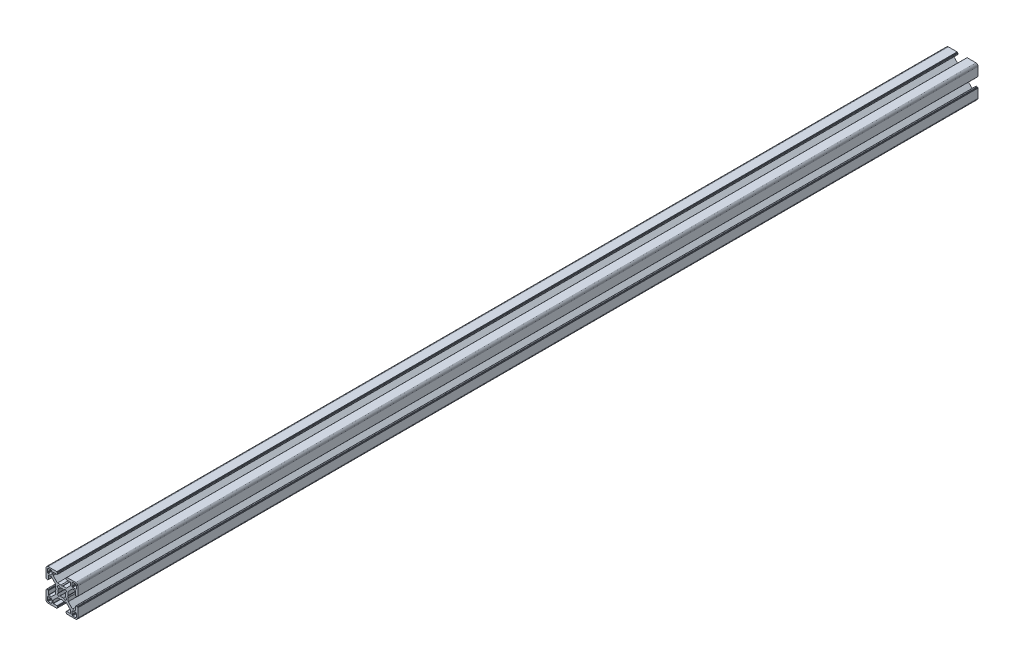
SolidWorks part; units mm, degrees
ref_plane "Front Plane" through (0, 0, 0) normal (0, 0, 1) x (1, 0, 0)
ref_plane "Top Plane" through (0, 0, 0) normal (0, 1, 0) x (1, 0, 0)
ref_plane "Right Plane" through (0, 0, 0) normal (1, 0, 0) x (0, 0, -1)
ref_plane "Plane1" through (0, 0, 0) normal (0, 0, 1) x (1, 0, 0)
sketch "Sketch1" plane through (0, 0, 0) normal (0, 0, 1) x (1, 0, 0)
  line L0 (28.3473, 29.9696) -> (28, 30)
  line L1 (28, 30) -> (19.75, 30)
  line L2 (19.75, 30) -> (19.7153, 29.997)
  line L3 (19.7153, 29.997) -> (19.6816, 29.9879)
  line L4 (19.6816, 29.9879) -> (19.65, 29.9732)
  line L5 (19.65, 29.9732) -> (19.6214, 29.9532)
  line L6 (19.6214, 29.9532) -> (19.5968, 29.9286)
  line L7 (19.5968, 29.9286) -> (19.5768, 29.9)
  line L8 (19.5768, 29.9) -> (19.5621, 29.8684)
  line L9 (19.5621, 29.8684) -> (19.553, 29.8347)
  line L10 (19.553, 29.8347) -> (19.55, 29.8)
  line L11 (19.55, 29.8) -> (19.55, 29.7)
  line L12 (19.55, 29.7) -> (19.547, 29.6653)
  line L13 (19.547, 29.6653) -> (19.5379, 29.6316)
  line L14 (19.5379, 29.6316) -> (19.5232, 29.6)
  line L15 (19.5232, 29.6) -> (19.5032, 29.5714)
  line L16 (19.5032, 29.5714) -> (19.4786, 29.5468)
  line L17 (19.4786, 29.5468) -> (19.45, 29.5268)
  line L18 (19.45, 29.5268) -> (19.4184, 29.5121)
  line L19 (19.4184, 29.5121) -> (19.3847, 29.503)
  line L20 (19.3847, 29.503) -> (19.35, 29.5)
  line L21 (19.35, 29.5) -> (19.25, 29.5)
  line L22 (19.25, 29.5) -> (19.2153, 29.497)
  line L23 (19.2153, 29.497) -> (19.1816, 29.4879)
  line L24 (19.1816, 29.4879) -> (19.15, 29.4732)
  line L25 (19.15, 29.4732) -> (19.1214, 29.4532)
  line L26 (19.1214, 29.4532) -> (19.0968, 29.4286)
  line L27 (19.0968, 29.4286) -> (19.0768, 29.4)
  line L28 (19.0768, 29.4) -> (19.0621, 29.3684)
  line L29 (19.0621, 29.3684) -> (19.053, 29.3347)
  line L30 (19.053, 29.3347) -> (19.05, 29.3)
  line L31 (19.05, 29.3) -> (19.05, 28.4)
  line L32 (19.05, 28.4) -> (19.0591, 28.2958)
  line L33 (19.0591, 28.2958) -> (19.0862, 28.1948)
  line L34 (19.0862, 28.1948) -> (19.1304, 28.1)
  line L35 (19.1304, 28.1) -> (19.1904, 28.0143)
  line L36 (19.1904, 28.0143) -> (19.2643, 27.9404)
  line L37 (19.2643, 27.9404) -> (19.35, 27.8804)
  line L38 (19.35, 27.8804) -> (19.4448, 27.8362)
  line L39 (19.4448, 27.8362) -> (19.5458, 27.8091)
  line L40 (19.5458, 27.8091) -> (19.65, 27.8)
  line L41 (19.65, 27.8) -> (23.05, 27.8)
  line L42 (23.05, 27.8) -> (23.0847, 27.7969)
  line L43 (23.0847, 27.7969) -> (23.1184, 27.7879)
  line L44 (23.1184, 27.7879) -> (23.15, 27.7732)
  line L45 (23.15, 27.7732) -> (23.1786, 27.7532)
  line L46 (23.1786, 27.7532) -> (23.2032, 27.7285)
  line L47 (23.2032, 27.7285) -> (23.2232, 27.7)
  line L48 (23.2232, 27.7) -> (23.2379, 27.6684)
  line L49 (23.2379, 27.6684) -> (23.247, 27.6347)
  line L50 (23.247, 27.6347) -> (23.25, 27.6)
  line L51 (23.25, 27.6) -> (23.25, 25.05)
  line L52 (23.25, 25.05) -> (19.2045, 21)
  line L53 (19.2045, 21) -> (15.9, 21)
  line L54 (15.9, 21) -> (15, 20.4848)
  line L55 (15, 20.4848) -> (14.1, 21)
  line L56 (14.1, 21) -> (10.7955, 21)
  line L57 (10.7955, 21) -> (7.9973, 23.8013)
  line L58 (7.9973, 23.8013) -> (6.75, 25.05)
  line L59 (6.75, 25.05) -> (6.75, 27.6)
  line L60 (6.75, 27.6) -> (6.753, 27.6347)
  line L61 (6.753, 27.6347) -> (6.7621, 27.6684)
  line L62 (6.7621, 27.6684) -> (6.7768, 27.7)
  line L63 (6.7768, 27.7) -> (6.7968, 27.7285)
  line L64 (6.7968, 27.7285) -> (6.8215, 27.7532)
  line L65 (6.8215, 27.7532) -> (6.85, 27.7732)
  line L66 (6.85, 27.7732) -> (6.8816, 27.7879)
  line L67 (6.8816, 27.7879) -> (6.9153, 27.7969)
  line L68 (6.9153, 27.7969) -> (6.95, 27.8)
  line L69 (6.95, 27.8) -> (10.35, 27.8)
  line L70 (10.35, 27.8) -> (10.4542, 27.8091)
  line L71 (10.4542, 27.8091) -> (10.5552, 27.8362)
  line L72 (10.5552, 27.8362) -> (10.65, 27.8804)
  line L73 (10.65, 27.8804) -> (10.7357, 27.9404)
  line L74 (10.7357, 27.9404) -> (10.8096, 28.0143)
  line L75 (10.8096, 28.0143) -> (10.8696, 28.1)
  line L76 (10.8696, 28.1) -> (10.9138, 28.1948)
  line L77 (10.9138, 28.1948) -> (10.9409, 28.2958)
  line L78 (10.9409, 28.2958) -> (10.95, 28.4)
  line L79 (10.95, 28.4) -> (10.95, 29.3)
  line L80 (10.95, 29.3) -> (10.947, 29.3347)
  line L81 (10.947, 29.3347) -> (10.938, 29.3684)
  line L82 (10.938, 29.3684) -> (10.9232, 29.4)
  line L83 (10.9232, 29.4) -> (10.9032, 29.4286)
  line L84 (10.9032, 29.4286) -> (10.8786, 29.4532)
  line L85 (10.8786, 29.4532) -> (10.85, 29.4732)
  line L86 (10.85, 29.4732) -> (10.8184, 29.4879)
  line L87 (10.8184, 29.4879) -> (10.7847, 29.497)
  line L88 (10.7847, 29.497) -> (10.75, 29.5)
  line L89 (10.75, 29.5) -> (10.65, 29.5)
  line L90 (10.65, 29.5) -> (10.6153, 29.503)
  line L91 (10.6153, 29.503) -> (10.5816, 29.5121)
  line L92 (10.5816, 29.5121) -> (10.55, 29.5268)
  line L93 (10.55, 29.5268) -> (10.5214, 29.5468)
  line L94 (10.5214, 29.5468) -> (10.4968, 29.5714)
  line L95 (10.4968, 29.5714) -> (10.4768, 29.6)
  line L96 (10.4768, 29.6) -> (10.4621, 29.6316)
  line L97 (10.4621, 29.6316) -> (10.453, 29.6653)
  line L98 (10.453, 29.6653) -> (10.45, 29.7)
  line L99 (10.45, 29.7) -> (10.45, 29.8)
  line L100 (10.45, 29.8) -> (10.447, 29.8347)
  line L101 (10.447, 29.8347) -> (10.4379, 29.8684)
  line L102 (10.4379, 29.8684) -> (10.4232, 29.9)
  line L103 (10.4232, 29.9) -> (10.4032, 29.9286)
  line L104 (10.4032, 29.9286) -> (10.3786, 29.9532)
  line L105 (10.3786, 29.9532) -> (10.35, 29.9732)
  line L106 (10.35, 29.9732) -> (10.3184, 29.9879)
  line L107 (10.3184, 29.9879) -> (10.2847, 29.997)
  line L108 (10.2847, 29.997) -> (10.25, 30)
  line L109 (10.25, 30) -> (2, 30)
  line L110 (2, 30) -> (1.6527, 29.9696)
  line L111 (1.6527, 29.9696) -> (1.316, 29.8794)
  line L112 (1.316, 29.8794) -> (1, 29.7321)
  line L113 (1, 29.7321) -> (0.7144, 29.5321)
  line L114 (0.7144, 29.5321) -> (0.4679, 29.2856)
  line L115 (0.4679, 29.2856) -> (0.2679, 29)
  line L116 (0.2679, 29) -> (0.1206, 28.684)
  line L117 (0.1206, 28.684) -> (0.0304, 28.3473)
  line L118 (0.0304, 28.3473) -> (0, 28)
  line L119 (0, 28) -> (0, 19.75)
  line L120 (0, 19.75) -> (0.003, 19.7153)
  line L121 (0.003, 19.7153) -> (0.0121, 19.6816)
  line L122 (0.0121, 19.6816) -> (0.0268, 19.65)
  line L123 (0.0268, 19.65) -> (0.0468, 19.6214)
  line L124 (0.0468, 19.6214) -> (0.0714, 19.5968)
  line L125 (0.0714, 19.5968) -> (0.1, 19.5768)
  line L126 (0.1, 19.5768) -> (0.1316, 19.5621)
  line L127 (0.1316, 19.5621) -> (0.1653, 19.553)
  line L128 (0.1653, 19.553) -> (0.2, 19.55)
  line L129 (0.2, 19.55) -> (0.3, 19.55)
  line L130 (0.3, 19.55) -> (0.3347, 19.547)
  line L131 (0.3347, 19.547) -> (0.3684, 19.5379)
  line L132 (0.3684, 19.5379) -> (0.4, 19.5232)
  line L133 (0.4, 19.5232) -> (0.4286, 19.5032)
  line L134 (0.4286, 19.5032) -> (0.4532, 19.4786)
  line L135 (0.4532, 19.4786) -> (0.4732, 19.45)
  line L136 (0.4732, 19.45) -> (0.4879, 19.4184)
  line L137 (0.4879, 19.4184) -> (0.497, 19.3847)
  line L138 (0.497, 19.3847) -> (0.5, 19.35)
  line L139 (0.5, 19.35) -> (0.5, 19.25)
  line L140 (0.5, 19.25) -> (0.503, 19.2153)
  line L141 (0.503, 19.2153) -> (0.5121, 19.1816)
  line L142 (0.5121, 19.1816) -> (0.5268, 19.15)
  line L143 (0.5268, 19.15) -> (0.5468, 19.1214)
  line L144 (0.5468, 19.1214) -> (0.5714, 19.0968)
  line L145 (0.5714, 19.0968) -> (0.6, 19.0768)
  line L146 (0.6, 19.0768) -> (0.6316, 19.0621)
  line L147 (0.6316, 19.0621) -> (0.6653, 19.053)
  line L148 (0.6653, 19.053) -> (0.7, 19.05)
  line L149 (0.7, 19.05) -> (1.6, 19.05)
  line L150 (1.6, 19.05) -> (1.7042, 19.0591)
  line L151 (1.7042, 19.0591) -> (1.8052, 19.0862)
  line L152 (1.8052, 19.0862) -> (1.9, 19.1304)
  line L153 (1.9, 19.1304) -> (1.9857, 19.1904)
  line L154 (1.9857, 19.1904) -> (2.0596, 19.2643)
  line L155 (2.0596, 19.2643) -> (2.1196, 19.35)
  line L156 (2.1196, 19.35) -> (2.1638, 19.4448)
  line L157 (2.1638, 19.4448) -> (2.1909, 19.5458)
  line L158 (2.1909, 19.5458) -> (2.2, 19.65)
  line L159 (2.2, 19.65) -> (2.2, 23.05)
  line L160 (2.2, 23.05) -> (2.203, 23.0847)
  line L161 (2.203, 23.0847) -> (2.2121, 23.1184)
  line L162 (2.2121, 23.1184) -> (2.2268, 23.15)
  line L163 (2.2268, 23.15) -> (2.2468, 23.1786)
  line L164 (2.2468, 23.1786) -> (2.2714, 23.2032)
  line L165 (2.2714, 23.2032) -> (2.3, 23.2232)
  line L166 (2.3, 23.2232) -> (2.3316, 23.2379)
  line L167 (2.3316, 23.2379) -> (2.3653, 23.247)
  line L168 (2.3653, 23.247) -> (2.4, 23.25)
  line L169 (2.4, 23.25) -> (4.95, 23.25)
  line L170 (4.95, 23.25) -> (7.9973, 20.2027)
  line L171 (7.9973, 20.2027) -> (8.9955, 19.2045)
  line L172 (8.9955, 19.2045) -> (8.9955, 15.9)
  line L173 (8.9955, 15.9) -> (9.5151, 15)
  line L174 (9.5151, 15) -> (8.9955, 14.1)
  line L175 (8.9955, 14.1) -> (8.9955, 10.7955)
  line L176 (8.9955, 10.7955) -> (4.95, 6.75)
  line L177 (4.95, 6.75) -> (2.4, 6.75)
  line L178 (2.4, 6.75) -> (2.3653, 6.753)
  line L179 (2.3653, 6.753) -> (2.3316, 6.7621)
  line L180 (2.3316, 6.7621) -> (2.3, 6.7768)
  line L181 (2.3, 6.7768) -> (2.2714, 6.7968)
  line L182 (2.2714, 6.7968) -> (2.2468, 6.8214)
  line L183 (2.2468, 6.8214) -> (2.2268, 6.85)
  line L184 (2.2268, 6.85) -> (2.2121, 6.8816)
  line L185 (2.2121, 6.8816) -> (2.203, 6.9153)
  line L186 (2.203, 6.9153) -> (2.2, 6.95)
  line L187 (2.2, 6.95) -> (2.2, 10.35)
  line L188 (2.2, 10.35) -> (2.1909, 10.4542)
  line L189 (2.1909, 10.4542) -> (2.1638, 10.5552)
  line L190 (2.1638, 10.5552) -> (2.1196, 10.65)
  line L191 (2.1196, 10.65) -> (2.0596, 10.7357)
  line L192 (2.0596, 10.7357) -> (1.9857, 10.8096)
  line L193 (1.9857, 10.8096) -> (1.9, 10.8696)
  line L194 (1.9, 10.8696) -> (1.8052, 10.9138)
  line L195 (1.8052, 10.9138) -> (1.7042, 10.9409)
  line L196 (1.7042, 10.9409) -> (1.6, 10.95)
  line L197 (1.6, 10.95) -> (0.7, 10.95)
  line L198 (0.7, 10.95) -> (0.6653, 10.9469)
  line L199 (0.6653, 10.9469) -> (0.6316, 10.9379)
  line L200 (0.6316, 10.9379) -> (0.6, 10.9232)
  line L201 (0.6, 10.9232) -> (0.5715, 10.9032)
  line L202 (0.5715, 10.9032) -> (0.5468, 10.8785)
  line L203 (0.5468, 10.8785) -> (0.5268, 10.85)
  line L204 (0.5268, 10.85) -> (0.5121, 10.8184)
  line L205 (0.5121, 10.8184) -> (0.503, 10.7847)
  line L206 (0.503, 10.7847) -> (0.5, 10.75)
  line L207 (0.5, 10.75) -> (0.5, 10.65)
  line L208 (0.5, 10.65) -> (0.497, 10.6153)
  line L209 (0.497, 10.6153) -> (0.4879, 10.5816)
  line L210 (0.4879, 10.5816) -> (0.4732, 10.55)
  line L211 (0.4732, 10.55) -> (0.4532, 10.5214)
  line L212 (0.4532, 10.5214) -> (0.4286, 10.4968)
  line L213 (0.4286, 10.4968) -> (0.4, 10.4768)
  line L214 (0.4, 10.4768) -> (0.3684, 10.4621)
  line L215 (0.3684, 10.4621) -> (0.3347, 10.453)
  line L216 (0.3347, 10.453) -> (0.3, 10.45)
  line L217 (0.3, 10.45) -> (0.2, 10.45)
  line L218 (0.2, 10.45) -> (0.1653, 10.447)
  line L219 (0.1653, 10.447) -> (0.1316, 10.4379)
  line L220 (0.1316, 10.4379) -> (0.1, 10.4232)
  line L221 (0.1, 10.4232) -> (0.0714, 10.4032)
  line L222 (0.0714, 10.4032) -> (0.0468, 10.3786)
  line L223 (0.0468, 10.3786) -> (0.0268, 10.35)
  line L224 (0.0268, 10.35) -> (0.0121, 10.3184)
  line L225 (0.0121, 10.3184) -> (0.003, 10.2847)
  line L226 (0.003, 10.2847) -> (0, 10.25)
  line L227 (0, 10.25) -> (0, 2)
  line L228 (0, 2) -> (0.0304, 1.6527)
  line L229 (0.0304, 1.6527) -> (0.1206, 1.316)
  line L230 (0.1206, 1.316) -> (0.2679, 1)
  line L231 (0.2679, 1) -> (0.4679, 0.7144)
  line L232 (0.4679, 0.7144) -> (0.7144, 0.4679)
  line L233 (0.7144, 0.4679) -> (1, 0.2679)
  line L234 (1, 0.2679) -> (1.316, 0.1206)
  line L235 (1.316, 0.1206) -> (1.6527, 0.0304)
  line L236 (1.6527, 0.0304) -> (2, 0)
  line L237 (2, 0) -> (10.25, 0)
  line L238 (10.25, 0) -> (10.2847, 0.003)
  line L239 (10.2847, 0.003) -> (10.3184, 0.0121)
  line L240 (10.3184, 0.0121) -> (10.35, 0.0268)
  line L241 (10.35, 0.0268) -> (10.3786, 0.0468)
  line L242 (10.3786, 0.0468) -> (10.4032, 0.0714)
  line L243 (10.4032, 0.0714) -> (10.4232, 0.1)
  line L244 (10.4232, 0.1) -> (10.4379, 0.1316)
  line L245 (10.4379, 0.1316) -> (10.447, 0.1653)
  line L246 (10.447, 0.1653) -> (10.45, 0.2)
  line L247 (10.45, 0.2) -> (10.45, 0.3)
  line L248 (10.45, 0.3) -> (10.453, 0.3347)
  line L249 (10.453, 0.3347) -> (10.4621, 0.3684)
  line L250 (10.4621, 0.3684) -> (10.4768, 0.4)
  line L251 (10.4768, 0.4) -> (10.4968, 0.4286)
  line L252 (10.4968, 0.4286) -> (10.5214, 0.4532)
  line L253 (10.5214, 0.4532) -> (10.55, 0.4732)
  line L254 (10.55, 0.4732) -> (10.5816, 0.4879)
  line L255 (10.5816, 0.4879) -> (10.6153, 0.497)
  line L256 (10.6153, 0.497) -> (10.65, 0.5)
  line L257 (10.65, 0.5) -> (10.75, 0.5)
  line L258 (10.75, 0.5) -> (10.7847, 0.503)
  line L259 (10.7847, 0.503) -> (10.8184, 0.5121)
  line L260 (10.8184, 0.5121) -> (10.85, 0.5268)
  line L261 (10.85, 0.5268) -> (10.8785, 0.5468)
  line L262 (10.8785, 0.5468) -> (10.9032, 0.5715)
  line L263 (10.9032, 0.5715) -> (10.9232, 0.6)
  line L264 (10.9232, 0.6) -> (10.9379, 0.6316)
  line L265 (10.9379, 0.6316) -> (10.9469, 0.6653)
  line L266 (10.9469, 0.6653) -> (10.95, 0.7)
  line L267 (10.95, 0.7) -> (10.95, 1.6)
  line L268 (10.95, 1.6) -> (10.9409, 1.7042)
  line L269 (10.9409, 1.7042) -> (10.9138, 1.8052)
  line L270 (10.9138, 1.8052) -> (10.8696, 1.9)
  line L271 (10.8696, 1.9) -> (10.8096, 1.9857)
  line L272 (10.8096, 1.9857) -> (10.7357, 2.0596)
  line L273 (10.7357, 2.0596) -> (10.65, 2.1196)
  line L274 (10.65, 2.1196) -> (10.5552, 2.1638)
  line L275 (10.5552, 2.1638) -> (10.4542, 2.1909)
  line L276 (10.4542, 2.1909) -> (10.35, 2.2)
  line L277 (10.35, 2.2) -> (6.95, 2.2)
  line L278 (6.95, 2.2) -> (6.9153, 2.203)
  line L279 (6.9153, 2.203) -> (6.8816, 2.212)
  line L280 (6.8816, 2.212) -> (6.85, 2.2268)
  line L281 (6.85, 2.2268) -> (6.8215, 2.2468)
  line L282 (6.8215, 2.2468) -> (6.7968, 2.2714)
  line L283 (6.7968, 2.2714) -> (6.7768, 2.3)
  line L284 (6.7768, 2.3) -> (6.7621, 2.3316)
  line L285 (6.7621, 2.3316) -> (6.753, 2.3653)
  line L286 (6.753, 2.3653) -> (6.75, 2.4)
  line L287 (6.75, 2.4) -> (6.75, 4.95)
  line L288 (6.75, 4.95) -> (9.7875, 7.9908)
  line L289 (9.7875, 7.9908) -> (10.7955, 9)
  line L290 (10.7955, 9) -> (14.1, 9)
  line L291 (14.1, 9) -> (15, 9.5151)
  line L292 (15, 9.5151) -> (15.9, 9)
  line L293 (15.9, 9) -> (19.2045, 9)
  line L294 (19.2045, 9) -> (20.2126, 7.9908)
  line L295 (20.2126, 7.9908) -> (23.25, 4.95)
  line L296 (23.25, 4.95) -> (23.25, 2.4)
  line L297 (23.25, 2.4) -> (23.247, 2.3653)
  line L298 (23.247, 2.3653) -> (23.2379, 2.3316)
  line L299 (23.2379, 2.3316) -> (23.2232, 2.3)
  line L300 (23.2232, 2.3) -> (23.2032, 2.2714)
  line L301 (23.2032, 2.2714) -> (23.1786, 2.2468)
  line L302 (23.1786, 2.2468) -> (23.15, 2.2268)
  line L303 (23.15, 2.2268) -> (23.1184, 2.212)
  line L304 (23.1184, 2.212) -> (23.0847, 2.203)
  line L305 (23.0847, 2.203) -> (23.05, 2.2)
  line L306 (23.05, 2.2) -> (19.65, 2.2)
  line L307 (19.65, 2.2) -> (19.5458, 2.1909)
  line L308 (19.5458, 2.1909) -> (19.4448, 2.1638)
  line L309 (19.4448, 2.1638) -> (19.35, 2.1196)
  line L310 (19.35, 2.1196) -> (19.2643, 2.0596)
  line L311 (19.2643, 2.0596) -> (19.1904, 1.9857)
  line L312 (19.1904, 1.9857) -> (19.1304, 1.9)
  line L313 (19.1304, 1.9) -> (19.0862, 1.8052)
  line L314 (19.0862, 1.8052) -> (19.0591, 1.7042)
  line L315 (19.0591, 1.7042) -> (19.05, 1.6)
  line L316 (19.05, 1.6) -> (19.05, 0.7)
  line L317 (19.05, 0.7) -> (19.053, 0.6653)
  line L318 (19.053, 0.6653) -> (19.0621, 0.6316)
  line L319 (19.0621, 0.6316) -> (19.0768, 0.6)
  line L320 (19.0768, 0.6) -> (19.0968, 0.5714)
  line L321 (19.0968, 0.5714) -> (19.1214, 0.5468)
  line L322 (19.1214, 0.5468) -> (19.15, 0.5268)
  line L323 (19.15, 0.5268) -> (19.1816, 0.5121)
  line L324 (19.1816, 0.5121) -> (19.2153, 0.503)
  line L325 (19.2153, 0.503) -> (19.25, 0.5)
  line L326 (19.25, 0.5) -> (19.35, 0.5)
  line L327 (19.35, 0.5) -> (19.3847, 0.497)
  line L328 (19.3847, 0.497) -> (19.4184, 0.4879)
  line L329 (19.4184, 0.4879) -> (19.45, 0.4732)
  line L330 (19.45, 0.4732) -> (19.4786, 0.4532)
  line L331 (19.4786, 0.4532) -> (19.5032, 0.4286)
  line L332 (19.5032, 0.4286) -> (19.5232, 0.4)
  line L333 (19.5232, 0.4) -> (19.5379, 0.3684)
  line L334 (19.5379, 0.3684) -> (19.547, 0.3347)
  line L335 (19.547, 0.3347) -> (19.55, 0.3)
  line L336 (19.55, 0.3) -> (19.55, 0.2)
  line L337 (19.55, 0.2) -> (19.553, 0.1653)
  line L338 (19.553, 0.1653) -> (19.5621, 0.1316)
  line L339 (19.5621, 0.1316) -> (19.5768, 0.1)
  line L340 (19.5768, 0.1) -> (19.5968, 0.0714)
  line L341 (19.5968, 0.0714) -> (19.6214, 0.0468)
  line L342 (19.6214, 0.0468) -> (19.65, 0.0268)
  line L343 (19.65, 0.0268) -> (19.6816, 0.0121)
  line L344 (19.6816, 0.0121) -> (19.7153, 0.003)
  line L345 (19.7153, 0.003) -> (19.75, 0)
  line L346 (19.75, 0) -> (28, 0)
  line L347 (28, 0) -> (28.3473, 0.0304)
  line L348 (28.3473, 0.0304) -> (28.684, 0.1206)
  line L349 (28.684, 0.1206) -> (29, 0.2679)
  line L350 (29, 0.2679) -> (29.2856, 0.4679)
  line L351 (29.2856, 0.4679) -> (29.5321, 0.7144)
  line L352 (29.5321, 0.7144) -> (29.7321, 1)
  line L353 (29.7321, 1) -> (29.8794, 1.316)
  line L354 (29.8794, 1.316) -> (29.9696, 1.6527)
  line L355 (29.9696, 1.6527) -> (30, 2)
  line L356 (30, 2) -> (30, 10.25)
  line L357 (30, 10.25) -> (29.997, 10.2847)
  line L358 (29.997, 10.2847) -> (29.988, 10.3184)
  line L359 (29.988, 10.3184) -> (29.9732, 10.35)
  line L360 (29.9732, 10.35) -> (29.9532, 10.3785)
  line L361 (29.9532, 10.3785) -> (29.9286, 10.4032)
  line L362 (29.9286, 10.4032) -> (29.9, 10.4232)
  line L363 (29.9, 10.4232) -> (29.8684, 10.4379)
  line L364 (29.8684, 10.4379) -> (29.8347, 10.447)
  line L365 (29.8347, 10.447) -> (29.8, 10.45)
  line L366 (29.8, 10.45) -> (29.7, 10.45)
  line L367 (29.7, 10.45) -> (29.6649, 10.4534)
  line L368 (29.6649, 10.4534) -> (29.6312, 10.4624)
  line L369 (29.6312, 10.4624) -> (29.5996, 10.4772)
  line L370 (29.5996, 10.4772) -> (29.5711, 10.4972)
  line L371 (29.5711, 10.4972) -> (29.5464, 10.5218)
  line L372 (29.5464, 10.5218) -> (29.5264, 10.5504)
  line L373 (29.5264, 10.5504) -> (29.5117, 10.582)
  line L374 (29.5117, 10.582) -> (29.5027, 10.6156)
  line L375 (29.5027, 10.6156) -> (29.4996, 10.6504)
  line L376 (29.4996, 10.6504) -> (29.4996, 10.7504)
  line L377 (29.4996, 10.7504) -> (29.497, 10.7847)
  line L378 (29.497, 10.7847) -> (29.4879, 10.8184)
  line L379 (29.4879, 10.8184) -> (29.4732, 10.85)
  line L380 (29.4732, 10.85) -> (29.4532, 10.8785)
  line L381 (29.4532, 10.8785) -> (29.4286, 10.9032)
  line L382 (29.4286, 10.9032) -> (29.4, 10.9232)
  line L383 (29.4, 10.9232) -> (29.3684, 10.9379)
  line L384 (29.3684, 10.9379) -> (29.3347, 10.9469)
  line L385 (29.3347, 10.9469) -> (29.3, 10.95)
  line L386 (29.3, 10.95) -> (28.4, 10.95)
  line L387 (28.4, 10.95) -> (28.2958, 10.9409)
  line L388 (28.2958, 10.9409) -> (28.1948, 10.9138)
  line L389 (28.1948, 10.9138) -> (28.1, 10.8696)
  line L390 (28.1, 10.8696) -> (28.0143, 10.8096)
  line L391 (28.0143, 10.8096) -> (27.9404, 10.7357)
  line L392 (27.9404, 10.7357) -> (27.8804, 10.65)
  line L393 (27.8804, 10.65) -> (27.8362, 10.5552)
  line L394 (27.8362, 10.5552) -> (27.8091, 10.4542)
  line L395 (27.8091, 10.4542) -> (27.8, 10.35)
  line L396 (27.8, 10.35) -> (27.8, 6.95)
  line L397 (27.8, 6.95) -> (27.797, 6.9153)
  line L398 (27.797, 6.9153) -> (27.7879, 6.8816)
  line L399 (27.7879, 6.8816) -> (27.7732, 6.85)
  line L400 (27.7732, 6.85) -> (27.7532, 6.8214)
  line L401 (27.7532, 6.8214) -> (27.7286, 6.7968)
  line L402 (27.7286, 6.7968) -> (27.7, 6.7768)
  line L403 (27.7, 6.7768) -> (27.6684, 6.7621)
  line L404 (27.6684, 6.7621) -> (27.6347, 6.753)
  line L405 (27.6347, 6.753) -> (27.6, 6.75)
  line L406 (27.6, 6.75) -> (25.05, 6.75)
  line L407 (25.05, 6.75) -> (23.8092, 7.9908)
  line L408 (23.8092, 7.9908) -> (21.0045, 10.7955)
  line L409 (21.0045, 10.7955) -> (21.0045, 14.1)
  line L410 (21.0045, 14.1) -> (20.4849, 15)
  line L411 (20.4849, 15) -> (21.0045, 15.9)
  line L412 (21.0045, 15.9) -> (21.0045, 19.2045)
  line L413 (21.0045, 19.2045) -> (25.05, 23.25)
  line L414 (25.05, 23.25) -> (27.6, 23.25)
  line L415 (27.6, 23.25) -> (27.6347, 23.247)
  line L416 (27.6347, 23.247) -> (27.6684, 23.2379)
  line L417 (27.6684, 23.2379) -> (27.7, 23.2232)
  line L418 (27.7, 23.2232) -> (27.7286, 23.2032)
  line L419 (27.7286, 23.2032) -> (27.7532, 23.1786)
  line L420 (27.7532, 23.1786) -> (27.7732, 23.15)
  line L421 (27.7732, 23.15) -> (27.7879, 23.1184)
  line L422 (27.7879, 23.1184) -> (27.797, 23.0847)
  line L423 (27.797, 23.0847) -> (27.8, 23.05)
  line L424 (27.8, 23.05) -> (27.8, 19.65)
  line L425 (27.8, 19.65) -> (27.8091, 19.5458)
  line L426 (27.8091, 19.5458) -> (27.8362, 19.4448)
  line L427 (27.8362, 19.4448) -> (27.8804, 19.35)
  line L428 (27.8804, 19.35) -> (27.9404, 19.2643)
  line L429 (27.9404, 19.2643) -> (28.0143, 19.1904)
  line L430 (28.0143, 19.1904) -> (28.1, 19.1304)
  line L431 (28.1, 19.1304) -> (28.1948, 19.0862)
  line L432 (28.1948, 19.0862) -> (28.2958, 19.0591)
  line L433 (28.2958, 19.0591) -> (28.4, 19.05)
  line L434 (28.4, 19.05) -> (29.3, 19.05)
  line L435 (29.3, 19.05) -> (29.3347, 19.053)
  line L436 (29.3347, 19.053) -> (29.3684, 19.0621)
  line L437 (29.3684, 19.0621) -> (29.4, 19.0768)
  line L438 (29.4, 19.0768) -> (29.4282, 19.0971)
  line L439 (29.4282, 19.0971) -> (29.4528, 19.1218)
  line L440 (29.4528, 19.1218) -> (29.4728, 19.1504)
  line L441 (29.4728, 19.1504) -> (29.4876, 19.182)
  line L442 (29.4876, 19.182) -> (29.4966, 19.2156)
  line L443 (29.4966, 19.2156) -> (29.4996, 19.2504)
  line L444 (29.4996, 19.2504) -> (29.4996, 19.3504)
  line L445 (29.4996, 19.3504) -> (29.5027, 19.3851)
  line L446 (29.5027, 19.3851) -> (29.5117, 19.4188)
  line L447 (29.5117, 19.4188) -> (29.5264, 19.4504)
  line L448 (29.5264, 19.4504) -> (29.5464, 19.4789)
  line L449 (29.5464, 19.4789) -> (29.5711, 19.5036)
  line L450 (29.5711, 19.5036) -> (29.5996, 19.5236)
  line L451 (29.5996, 19.5236) -> (29.6312, 19.5383)
  line L452 (29.6312, 19.5383) -> (29.6649, 19.5473)
  line L453 (29.6649, 19.5473) -> (29.7, 19.55)
  line L454 (29.7, 19.55) -> (29.8, 19.55)
  line L455 (29.8, 19.55) -> (29.8347, 19.553)
  line L456 (29.8347, 19.553) -> (29.8684, 19.5621)
  line L457 (29.8684, 19.5621) -> (29.9, 19.5768)
  line L458 (29.9, 19.5768) -> (29.9286, 19.5968)
  line L459 (29.9286, 19.5968) -> (29.9532, 19.6214)
  line L460 (29.9532, 19.6214) -> (29.9732, 19.65)
  line L461 (29.9732, 19.65) -> (29.9879, 19.6816)
  line L462 (29.9879, 19.6816) -> (29.997, 19.7153)
  line L463 (29.997, 19.7153) -> (30, 19.75)
  line L464 (30, 19.75) -> (30, 28)
  line L465 (30, 28) -> (29.9696, 28.3473)
  line L466 (29.9696, 28.3473) -> (29.8794, 28.684)
  line L467 (29.8794, 28.684) -> (29.7321, 29)
  line L468 (29.7321, 29) -> (29.5321, 29.2856)
  line L469 (29.5321, 29.2856) -> (29.2856, 29.5321)
  line L470 (29.2856, 29.5321) -> (29, 29.7321)
  line L471 (29, 29.7321) -> (28.684, 29.8794)
  line L472 (28.684, 29.8794) -> (28.3473, 29.9696)
  line L473 (1.3, 25.5) -> (1.3, 27.7)
  line L474 (1.3, 27.7) -> (1.3123, 27.8564)
  line L475 (1.3123, 27.8564) -> (1.3489, 28.009)
  line L476 (1.3489, 28.009) -> (1.409, 28.154)
  line L477 (1.409, 28.154) -> (1.491, 28.2878)
  line L478 (1.491, 28.2878) -> (1.5929, 28.4071)
  line L479 (1.5929, 28.4071) -> (1.7122, 28.509)
  line L480 (1.7122, 28.509) -> (1.846, 28.591)
  line L481 (1.846, 28.591) -> (1.991, 28.6511)
  line L482 (1.991, 28.6511) -> (2.1436, 28.6877)
  line L483 (2.1436, 28.6877) -> (2.3, 28.7)
  line L484 (2.3, 28.7) -> (4.5, 28.7)
  line L485 (4.5, 28.7) -> (4.6564, 28.6877)
  line L486 (4.6564, 28.6877) -> (4.809, 28.6511)
  line L487 (4.809, 28.6511) -> (4.954, 28.591)
  line L488 (4.954, 28.591) -> (5.0878, 28.509)
  line L489 (5.0878, 28.509) -> (5.2071, 28.4071)
  line L490 (5.2071, 28.4071) -> (5.309, 28.2878)
  line L491 (5.309, 28.2878) -> (5.391, 28.154)
  line L492 (5.391, 28.154) -> (5.4511, 28.009)
  line L493 (5.4511, 28.009) -> (5.4877, 27.8564)
  line L494 (5.4877, 27.8564) -> (5.5, 27.7)
  line L495 (5.5, 27.7) -> (5.5, 25.5)
  line L496 (5.5, 25.5) -> (5.4877, 25.3436)
  line L497 (5.4877, 25.3436) -> (5.4511, 25.191)
  line L498 (5.4511, 25.191) -> (5.391, 25.046)
  line L499 (5.391, 25.046) -> (5.309, 24.9122)
  line L500 (5.309, 24.9122) -> (5.2071, 24.7929)
  line L501 (5.2071, 24.7929) -> (5.0878, 24.691)
  line L502 (5.0878, 24.691) -> (4.954, 24.609)
  line L503 (4.954, 24.609) -> (4.809, 24.5489)
  line L504 (4.809, 24.5489) -> (4.6564, 24.5123)
  line L505 (4.6564, 24.5123) -> (4.5, 24.5)
  line L506 (4.5, 24.5) -> (2.3, 24.5)
  line L507 (2.3, 24.5) -> (2.1436, 24.5123)
  line L508 (2.1436, 24.5123) -> (1.991, 24.5489)
  line L509 (1.991, 24.5489) -> (1.846, 24.609)
  line L510 (1.846, 24.609) -> (1.7122, 24.691)
  line L511 (1.7122, 24.691) -> (1.5929, 24.7929)
  line L512 (1.5929, 24.7929) -> (1.491, 24.9122)
  line L513 (1.491, 24.9122) -> (1.409, 25.046)
  line L514 (1.409, 25.046) -> (1.3489, 25.191)
  line L515 (1.3489, 25.191) -> (1.3123, 25.3436)
  line L516 (1.3123, 25.3436) -> (1.3, 25.5)
  line L517 (25.3436, 28.6877) -> (25.5, 28.7)
  line L518 (25.5, 28.7) -> (27.7, 28.7)
  line L519 (27.7, 28.7) -> (27.8564, 28.6877)
  line L520 (27.8564, 28.6877) -> (28.009, 28.6511)
  line L521 (28.009, 28.6511) -> (28.154, 28.591)
  line L522 (28.154, 28.591) -> (28.2878, 28.509)
  line L523 (28.2878, 28.509) -> (28.4071, 28.4071)
  line L524 (28.4071, 28.4071) -> (28.509, 28.2878)
  line L525 (28.509, 28.2878) -> (28.591, 28.154)
  line L526 (28.591, 28.154) -> (28.6511, 28.009)
  line L527 (28.6511, 28.009) -> (28.6877, 27.8564)
  line L528 (28.6877, 27.8564) -> (28.7, 27.7)
  line L529 (28.7, 27.7) -> (28.7, 25.5)
  line L530 (28.7, 25.5) -> (28.6877, 25.3436)
  line L531 (28.6877, 25.3436) -> (28.6511, 25.191)
  line L532 (28.6511, 25.191) -> (28.591, 25.046)
  line L533 (28.591, 25.046) -> (28.509, 24.9122)
  line L534 (28.509, 24.9122) -> (28.4071, 24.7929)
  line L535 (28.4071, 24.7929) -> (28.2878, 24.691)
  line L536 (28.2878, 24.691) -> (28.154, 24.609)
  line L537 (28.154, 24.609) -> (28.009, 24.5489)
  line L538 (28.009, 24.5489) -> (27.8564, 24.5123)
  line L539 (27.8564, 24.5123) -> (27.7, 24.5)
  line L540 (27.7, 24.5) -> (25.5, 24.5)
  line L541 (25.5, 24.5) -> (25.3436, 24.5123)
  line L542 (25.3436, 24.5123) -> (25.191, 24.5489)
  line L543 (25.191, 24.5489) -> (25.046, 24.609)
  line L544 (25.046, 24.609) -> (24.9122, 24.691)
  line L545 (24.9122, 24.691) -> (24.7929, 24.7929)
  line L546 (24.7929, 24.7929) -> (24.691, 24.9122)
  line L547 (24.691, 24.9122) -> (24.609, 25.046)
  line L548 (24.609, 25.046) -> (24.5489, 25.191)
  line L549 (24.5489, 25.191) -> (24.5123, 25.3436)
  line L550 (24.5123, 25.3436) -> (24.5, 25.5)
  line L551 (24.5, 25.5) -> (24.5, 27.7)
  line L552 (24.5, 27.7) -> (24.5123, 27.8564)
  line L553 (24.5123, 27.8564) -> (24.5489, 28.009)
  line L554 (24.5489, 28.009) -> (24.609, 28.154)
  line L555 (24.609, 28.154) -> (24.691, 28.2878)
  line L556 (24.691, 28.2878) -> (24.7929, 28.4071)
  line L557 (24.7929, 28.4071) -> (24.9122, 28.509)
  line L558 (24.9122, 28.509) -> (25.046, 28.591)
  line L559 (25.046, 28.591) -> (25.191, 28.6511)
  line L560 (25.191, 28.6511) -> (25.3436, 28.6877)
  line L561 (15, 18.65) -> (15.55, 18.6083)
  line L562 (15.55, 18.6083) -> (16.0875, 18.4842)
  line L563 (16.0875, 18.4842) -> (16.6001, 18.2806)
  line L564 (16.6001, 18.2806) -> (18.1359, 19.5184)
  line L565 (18.1359, 19.5184) -> (18.645, 19.1187)
  line L566 (18.645, 19.1187) -> (19.1036, 18.6621)
  line L567 (19.1036, 18.6621) -> (19.5053, 18.1547)
  line L568 (19.5053, 18.1547) -> (18.2806, 16.6001)
  line L569 (18.2806, 16.6001) -> (18.4842, 16.0875)
  line L570 (18.4842, 16.0875) -> (18.6083, 15.55)
  line L571 (18.6083, 15.55) -> (18.65, 15)
  line L572 (18.65, 15) -> (18.6083, 14.45)
  line L573 (18.6083, 14.45) -> (18.4842, 13.9125)
  line L574 (18.4842, 13.9125) -> (18.2806, 13.3999)
  line L575 (18.2806, 13.3999) -> (19.5053, 11.8453)
  line L576 (19.5053, 11.8453) -> (19.1036, 11.3379)
  line L577 (19.1036, 11.3379) -> (18.645, 10.8813)
  line L578 (18.645, 10.8813) -> (18.1359, 10.4816)
  line L579 (18.1359, 10.4816) -> (16.6001, 11.7194)
  line L580 (16.6001, 11.7194) -> (16.0875, 11.5158)
  line L581 (16.0875, 11.5158) -> (15.55, 11.3917)
  line L582 (15.55, 11.3917) -> (15, 11.35)
  line L583 (15, 11.35) -> (14.45, 11.3917)
  line L584 (14.45, 11.3917) -> (13.9125, 11.5158)
  line L585 (13.9125, 11.5158) -> (13.3999, 11.7194)
  line L586 (13.3999, 11.7194) -> (11.8641, 10.4816)
  line L587 (11.8641, 10.4816) -> (11.355, 10.8813)
  line L588 (11.355, 10.8813) -> (10.8964, 11.3379)
  line L589 (10.8964, 11.3379) -> (10.4947, 11.8453)
  line L590 (10.4947, 11.8453) -> (11.7194, 13.3999)
  line L591 (11.7194, 13.3999) -> (11.5158, 13.9125)
  line L592 (11.5158, 13.9125) -> (11.3917, 14.45)
  line L593 (11.3917, 14.45) -> (11.35, 15)
  line L594 (11.35, 15) -> (11.3917, 15.55)
  line L595 (11.3917, 15.55) -> (11.5158, 16.0875)
  line L596 (11.5158, 16.0875) -> (11.7194, 16.6001)
  line L597 (11.7194, 16.6001) -> (10.4947, 18.1547)
  line L598 (10.4947, 18.1547) -> (10.8964, 18.6621)
  line L599 (10.8964, 18.6621) -> (11.355, 19.1187)
  line L600 (11.355, 19.1187) -> (11.8641, 19.5184)
  line L601 (11.8641, 19.5184) -> (13.3999, 18.2806)
  line L602 (13.3999, 18.2806) -> (13.9125, 18.4842)
  line L603 (13.9125, 18.4842) -> (14.45, 18.6083)
  line L604 (14.45, 18.6083) -> (15, 18.65)
  line L605 (4.5, 1.3) -> (2.3, 1.3)
  line L606 (2.3, 1.3) -> (2.1436, 1.3123)
  line L607 (2.1436, 1.3123) -> (1.991, 1.3489)
  line L608 (1.991, 1.3489) -> (1.846, 1.409)
  line L609 (1.846, 1.409) -> (1.7122, 1.491)
  line L610 (1.7122, 1.491) -> (1.5929, 1.5929)
  line L611 (1.5929, 1.5929) -> (1.491, 1.7122)
  line L612 (1.491, 1.7122) -> (1.409, 1.846)
  line L613 (1.409, 1.846) -> (1.3489, 1.991)
  line L614 (1.3489, 1.991) -> (1.3123, 2.1436)
  line L615 (1.3123, 2.1436) -> (1.3, 2.3)
  line L616 (1.3, 2.3) -> (1.3, 4.5)
  line L617 (1.3, 4.5) -> (1.3123, 4.6564)
  line L618 (1.3123, 4.6564) -> (1.3489, 4.809)
  line L619 (1.3489, 4.809) -> (1.409, 4.954)
  line L620 (1.409, 4.954) -> (1.491, 5.0878)
  line L621 (1.491, 5.0878) -> (1.5929, 5.2071)
  line L622 (1.5929, 5.2071) -> (1.7122, 5.309)
  line L623 (1.7122, 5.309) -> (1.846, 5.391)
  line L624 (1.846, 5.391) -> (1.991, 5.4511)
  line L625 (1.991, 5.4511) -> (2.1436, 5.4877)
  line L626 (2.1436, 5.4877) -> (2.3, 5.5)
  line L627 (2.3, 5.5) -> (4.5, 5.5)
  line L628 (4.5, 5.5) -> (4.6564, 5.4877)
  line L629 (4.6564, 5.4877) -> (4.809, 5.4511)
  line L630 (4.809, 5.4511) -> (4.954, 5.391)
  line L631 (4.954, 5.391) -> (5.0878, 5.309)
  line L632 (5.0878, 5.309) -> (5.2071, 5.2071)
  line L633 (5.2071, 5.2071) -> (5.309, 5.0878)
  line L634 (5.309, 5.0878) -> (5.391, 4.954)
  line L635 (5.391, 4.954) -> (5.4511, 4.809)
  line L636 (5.4511, 4.809) -> (5.4877, 4.6564)
  line L637 (5.4877, 4.6564) -> (5.5, 4.5)
  line L638 (5.5, 4.5) -> (5.5, 2.3)
  line L639 (5.5, 2.3) -> (5.4877, 2.1436)
  line L640 (5.4877, 2.1436) -> (5.4511, 1.991)
  line L641 (5.4511, 1.991) -> (5.391, 1.846)
  line L642 (5.391, 1.846) -> (5.309, 1.7122)
  line L643 (5.309, 1.7122) -> (5.2071, 1.5929)
  line L644 (5.2071, 1.5929) -> (5.0878, 1.491)
  line L645 (5.0878, 1.491) -> (4.954, 1.409)
  line L646 (4.954, 1.409) -> (4.809, 1.3489)
  line L647 (4.809, 1.3489) -> (4.6564, 1.3123)
  line L648 (4.6564, 1.3123) -> (4.5, 1.3)
  line L649 (27.7, 1.3) -> (25.5, 1.3)
  line L650 (25.5, 1.3) -> (25.3436, 1.3123)
  line L651 (25.3436, 1.3123) -> (25.191, 1.3489)
  line L652 (25.191, 1.3489) -> (25.046, 1.409)
  line L653 (25.046, 1.409) -> (24.9122, 1.491)
  line L654 (24.9122, 1.491) -> (24.7929, 1.5929)
  line L655 (24.7929, 1.5929) -> (24.691, 1.7122)
  line L656 (24.691, 1.7122) -> (24.609, 1.846)
  line L657 (24.609, 1.846) -> (24.5489, 1.991)
  line L658 (24.5489, 1.991) -> (24.5123, 2.1436)
  line L659 (24.5123, 2.1436) -> (24.5, 2.3)
  line L660 (24.5, 2.3) -> (24.5, 4.5)
  line L661 (24.5, 4.5) -> (24.5123, 4.6564)
  line L662 (24.5123, 4.6564) -> (24.5489, 4.809)
  line L663 (24.5489, 4.809) -> (24.609, 4.954)
  line L664 (24.609, 4.954) -> (24.691, 5.0878)
  line L665 (24.691, 5.0878) -> (24.7929, 5.2071)
  line L666 (24.7929, 5.2071) -> (24.9122, 5.309)
  line L667 (24.9122, 5.309) -> (25.046, 5.391)
  line L668 (25.046, 5.391) -> (25.191, 5.4511)
  line L669 (25.191, 5.4511) -> (25.3436, 5.4877)
  line L670 (25.3436, 5.4877) -> (25.5, 5.5)
  line L671 (25.5, 5.5) -> (27.7, 5.5)
  line L672 (27.7, 5.5) -> (27.8564, 5.4877)
  line L673 (27.8564, 5.4877) -> (28.009, 5.4511)
  line L674 (28.009, 5.4511) -> (28.154, 5.391)
  line L675 (28.154, 5.391) -> (28.2878, 5.309)
  line L676 (28.2878, 5.309) -> (28.4071, 5.2071)
  line L677 (28.4071, 5.2071) -> (28.509, 5.0878)
  line L678 (28.509, 5.0878) -> (28.591, 4.954)
  line L679 (28.591, 4.954) -> (28.6511, 4.809)
  line L680 (28.6511, 4.809) -> (28.6877, 4.6564)
  line L681 (28.6877, 4.6564) -> (28.7, 4.5)
  line L682 (28.7, 4.5) -> (28.7, 2.3)
  line L683 (28.7, 2.3) -> (28.6877, 2.1436)
  line L684 (28.6877, 2.1436) -> (28.6511, 1.991)
  line L685 (28.6511, 1.991) -> (28.591, 1.846)
  line L686 (28.591, 1.846) -> (28.509, 1.7122)
  line L687 (28.509, 1.7122) -> (28.4071, 1.5929)
  line L688 (28.4071, 1.5929) -> (28.2878, 1.491)
  line L689 (28.2878, 1.491) -> (28.154, 1.409)
  line L690 (28.154, 1.409) -> (28.009, 1.3489)
  line L691 (28.009, 1.3489) -> (27.8564, 1.3123)
  line L692 (27.8564, 1.3123) -> (27.7, 1.3)
extrude "Boss-Extrude1" add sketch "Sketch1" against normal blind 850
